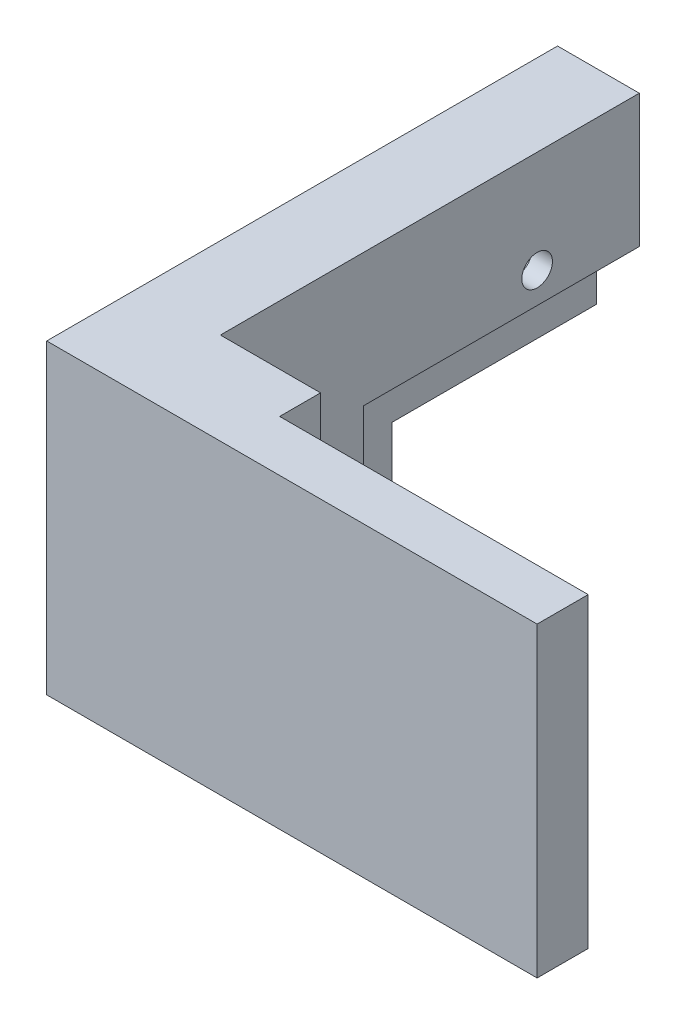
SolidWorks part; units mm, degrees
ref_plane "前视基准面" through (0, 0, 0) normal (0, 0, 1) x (1, 0, 0)
ref_plane "上视基准面" through (0, 0, 0) normal (0, 1, 0) x (1, 0, 0)
ref_plane "右视基准面" through (0, 0, 0) normal (1, 0, 0) x (0, 0, -1)
other "Configuration Table"
sketch "草图1" plane through (0, 0, 0) normal (0, 0, 1) x (1, 0, 0)
  line L1 (0, 0) -> (-40, 0)
  line L2 (0, 0) -> (0, 30)
  line L3 (0, 30) -> (-40, 30)
  line L4 (-40, 0) -> (-40, 30)
  dimension "D1" = 40
  dimension "D2" = 30
extrude "凸台-拉伸1" add sketch "草图1" along normal blind 5
sketch "草图2" plane through (-40, 0, 0) normal (-1, 0, 0) x (0, 0, 1)
  line L4 (0, 30) -> (0, 0)
  line L5 (0, 0) -> (5, 0)
  line L6 (5, 0) -> (5, 30)
  line L7 (5, 30) -> (0, 30)
  line L8 (0, 30) -> (0, 0)
  line L9 (0, 0) -> (5, 0)
  line L10 (5, 0) -> (5, 30)
  line L11 (5, 30) -> (0, 30)
  dimension "D1" = 0
extrude "凸台-拉伸2" add sketch "草图2" along normal blind 20
sketch "草图3" plane through (0, 0, 0) normal (0, 0, -1) x (-1, 0, 0)
  line L0 (60, 0) -> (0, 0) construction
  line L1 (60, 30) -> (40, 30)
  line L2 (60, 30) -> (60, 0)
  line L3 (60, 0) -> (40, 0)
  line L4 (40, 30) -> (40, 0)
  dimension "D1" = 20
extrude "凸台-拉伸3" add sketch "草图3" along normal blind 5
sketch "草图4" plane through (0, 0, 5) normal (0, 0, 1) x (1, 0, 0)
  line L0 (0, 30) -> (-60, 30) construction
  line L1 (-60, 30) -> (-45, 30)
  line L2 (-60, 30) -> (-60, 0)
  line L3 (-60, 0) -> (-45, 0)
  line L4 (-45, 30) -> (-45, 0)
  line L5 (-60, 0) -> (0, 0) construction
  line L6 (-60, 0) -> (-60, 30) construction
  dimension "D1" = 0
  dimension "D2" = 15
extrude "切除-拉伸1" cut sketch "草图4" against normal blind 5
sketch "草图5" plane through (0, 0, 0) normal (0, 0, 1) x (1, 0, 0)
  line L0 (-52.5, 30) -> (-52.5, 25) construction
  line L1 (-45, 30) -> (-60, 30) construction
  line L2 (-52.5, 25) -> (-52.5, 5) construction
  circle A0 centre (-52.5, 5) radius 1.5
  circle A1 centre (-52.5, 25) radius 1.5
  dimension "D3" = 3
  dimension "D4" = 3
  dimension "D1" = 5
  dimension "D2" = 20
extrude "切除-拉伸2" cut sketch "草图5" against normal blind 5
sketch "草图6" plane through (0, 0, 0) normal (0, 0, 1) x (1, 0, 0)
  circle A0 centre (-52.5, 25) radius 3
  circle A1 centre (-52.5, 5) radius 3
  dimension "D1" = 6
  dimension "D2" = 6
extrude "切除-拉伸3" cut sketch "草图6" against normal blind 2
sketch "草图7" plane through (0, 0, 0) normal (0, 0, 1) x (1, 0, 0)
  line L4 (-60, 30) -> (-60, 0)
  line L5 (-60, 0) -> (-45, 0)
  line L6 (-45, 0) -> (-45, 30)
  line L7 (-45, 30) -> (-60, 30)
  line L8 (-60, 30) -> (-60, 0)
  line L9 (-60, 0) -> (-45, 0)
  line L10 (-45, 0) -> (-45, 30)
  line L11 (-45, 30) -> (-60, 30)
  dimension "D1" = 0
extrude "切除-拉伸4" cut sketch "草图7" against normal blind 10
sketch "草图8" plane through (0, 0, -5) normal (0, 0, -1) x (-1, 0, 0)
  line L4 (40, 0) -> (45, 0)
  line L5 (45, 0) -> (45, 30)
  line L6 (45, 30) -> (40, 30)
  line L7 (40, 30) -> (40, 0)
  line L8 (40, 0) -> (45, 0)
  line L9 (45, 0) -> (45, 30)
  line L10 (45, 30) -> (40, 30)
  line L11 (40, 30) -> (40, 0)
  dimension "D1" = 0
extrude "凸台-拉伸4" add sketch "草图8" along normal blind 20
sketch "草图9" plane through (-40, 0, 0) normal (1, 0, 0) x (0, 0, -1)
  line L0 (25, 0) -> (0, 0) construction
  line L1 (25, 30) -> (18, 30)
  line L2 (25, 30) -> (25, 0)
  line L3 (25, 0) -> (18, 0)
  line L4 (18, 30) -> (18, 0)
  dimension "D1" = 7
sketch "草图10" plane through (-45, 0, 0) normal (-1, 0, 0) x (0, 0, 1)
  line L4 (5, 0) -> (5, 30)
  line L5 (5, 30) -> (-25, 30)
  line L6 (-25, 30) -> (-25, 0)
  line L7 (-25, 0) -> (5, 0)
  line L8 (5, 0) -> (5, 30)
  line L9 (5, 30) -> (-25, 30)
  line L10 (-25, 30) -> (-25, 0)
  line L11 (-25, 0) -> (5, 0)
  dimension "D1" = 0
extrude "凸台-拉伸5" add sketch "草图10" along normal blind 3
sketch "草图11" plane through (-48, 0, 0) normal (-1, 0, 0) x (0, 0, 1)
  line L0 (-25, 30) -> (-15, 30) construction
  line L1 (5, 30) -> (-25, 30) construction
  line L2 (-15, 30) -> (-15, 5) construction
  circle A0 centre (-15, 5) radius 1.5
  dimension "D4" = 3
  dimension "D1" = 25
  dimension "D3" = 10
extrude "切除-拉伸6" cut sketch "草图11" against normal blind 13
sketch "草图12" plane through (-48, 0, 0) normal (-1, 0, 0) x (0, 0, 1)
  circle A0 centre (-15, 5) radius 2.9
  dimension "D1" = 5.8
extrude "切除-拉伸7" cut sketch "草图12" against normal offset from surface (6 mm away) 2 up to face at (-40, 5, -13.5)
sketch "草图14" plane through (0, 0, -25) normal (0, 0, -1) x (-1, 0, 0)
  line L0 (40, 30) -> (40, 0) construction
  line L1 (48, 30) -> (40, 30)
  line L2 (48, 30) -> (48, 10)
  line L3 (48, 10) -> (40, 10)
  line L4 (40, 30) -> (40, 10)
  dimension "D1" = 20
extrude "凸台-拉伸6" add sketch "草图14" along normal blind 20
sketch "草图15" plane through (-40, 0, 0) normal (1, 0, 0) x (0, 0, -1)
  line L1 (45, 10) -> (25, 10)
  line L2 (45, 10) -> (45, 17)
  line L3 (45, 17) -> (18, 17)
  line L4 (18, 10) -> (18, 17)
  line L6 (18, 10) -> (18, 0)
  line L7 (18, 0) -> (25, 0)
  line L8 (25, 10) -> (25, 0)
  dimension "D1" = 7
  dimension "D2" = 7
extrude "切除-拉伸8" cut sketch "草图15" against normal blind 4.2
sketch "草图16" plane through (-48, 0, 0) normal (-1, 0, 0) x (0, 0, 1)
  line L0 (-45, 30) -> (-45, 20) construction
  line L1 (-45, 10) -> (-45, 30) construction
  line L2 (-45, 20) -> (-35, 20) construction
  circle A0 centre (-35, 20) radius 1.5
  dimension "D3" = 3
  dimension "D1" = 10
  dimension "D2" = 10
extrude "切除-拉伸9" cut sketch "草图16" against normal blind 14.2
sketch "草图17" plane through (-48, 0, 0) normal (-1, 0, 0) x (0, 0, 1)
  circle A0 centre (-35, 20) radius 2.9
  dimension "D1" = 5.8
extrude "切除-拉伸10" cut sketch "草图17" against normal offset from surface (6 mm away) 2 up to face at (-40, 20, -33.5)
sketch "草图18" plane through (-40, 0, 0) normal (1, 0, 0) x (0, 0, -1)
  line L0 (18, 0) -> (0, 0) construction
  line L1 (0, 30) -> (4, 30)
  line L2 (0, 30) -> (0, 0)
  line L3 (0, 0) -> (4, 0)
  line L4 (4, 30) -> (4, 0)
  dimension "D1" = 4
extrude "凸台-拉伸7" add sketch "草图18" along normal blind 9.8
